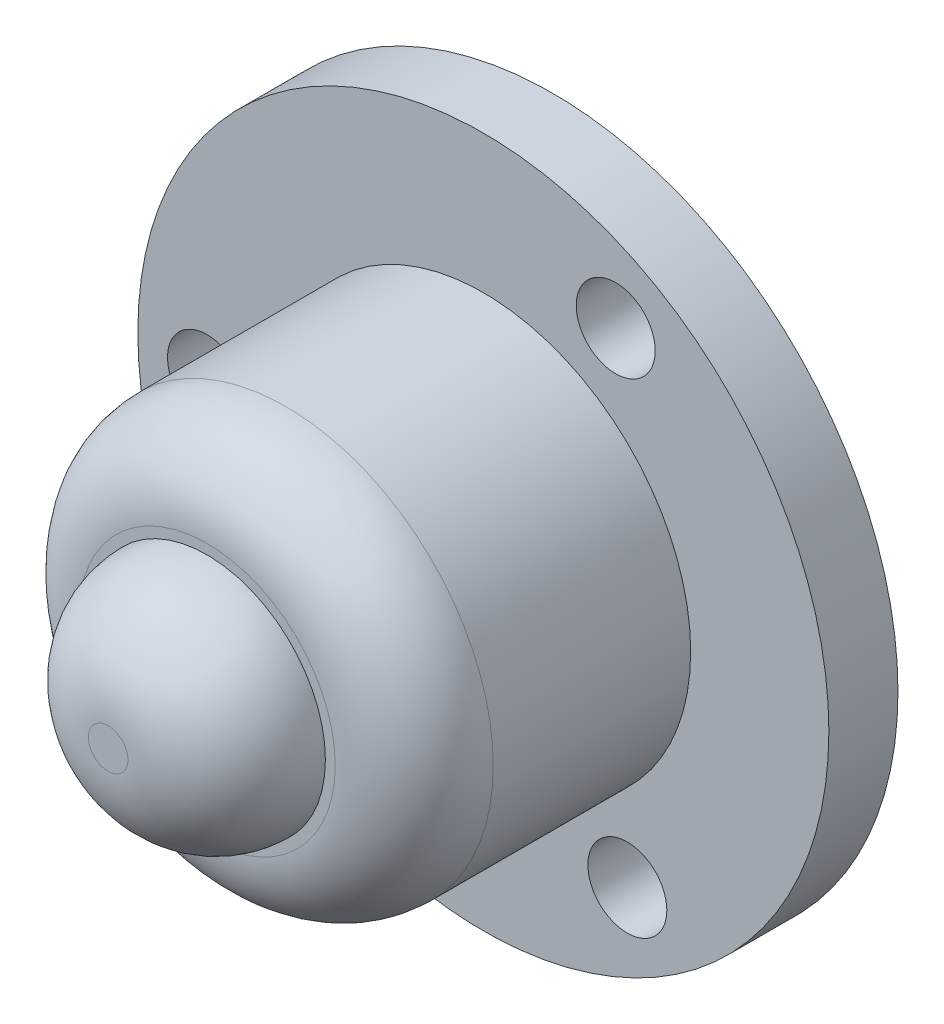
SolidWorks part; units mm, degrees
other "Markup1"
sketch "Sketch5" plane through (25, 25, 12) normal (0.2512, 0.4905, 0.8344) x (0.9318, -0.3559, -0.0713)
ref_plane "Front Plane" through (0, 0, 0) normal (0, 0, 1) x (1, 0, 0)
ref_plane "Top Plane" through (0, 0, 0) normal (0, 1, 0) x (1, 0, 0)
ref_plane "Right Plane" through (0, 0, 0) normal (1, 0, 0) x (0, 0, -1)
sketch "Sketch1" plane through (0, 0, 0) normal (0, 0, 1) x (1, 0, 0)
  circle A0 centre (0, 0) radius 17.5
  circle A1 centre (0, 0) radius 10
  circle A2 centre (0, 0) radius 14 construction
  circle A4 centre (6.7039, 12.2905) radius 2
  circle A6 centre (7.292, -11.951) radius 2
  circle A7 centre (-13.9959, -0.3395) radius 2
  point P14 (0, 0)
  dimension "D1" = 35
  dimension "D2" = 20
  dimension "D3" = 28
  dimension "D4" = 3
extrude "Boss-Extrude1" add sketch "Sketch1" along normal blind 3.5
sketch "Sketch3" plane through (0, 0, 3.5) normal (0, 0, 1) x (1, 0, 0)
  circle A0 centre (0, 0) radius 10.5
  dimension "D1" = 21
extrude "Boss-Extrude2" add sketch "Sketch3" along normal blind 14
fillet "Fillet1" radius 4 1 edges at (10.5, 0, 17.5)
sketch "Sketch4" plane through (0, 0, 17.5) normal (0, 0, 1) x (1, 0, 0)
  circle A0 centre (0, 0) radius 6
  dimension "D1" = 12
extrude "Boss-Extrude3" add sketch "Sketch4" along normal blind 5
fillet "Fillet2" radius 5 1 edges at (6, 0, 22.5)
